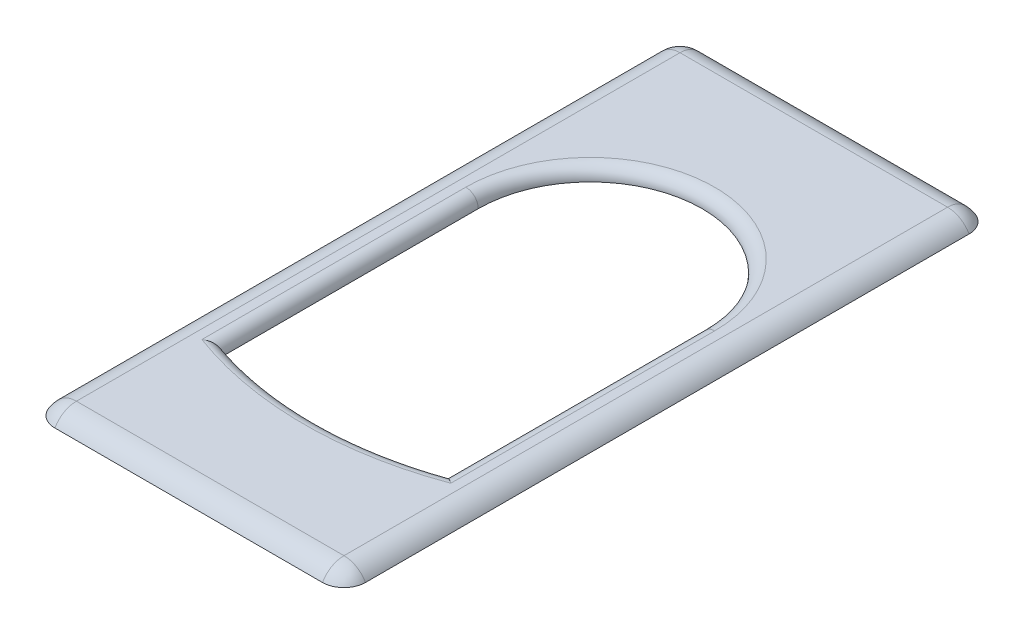
SolidWorks part; units mm, degrees
ref_plane "前视基准面" through (0, 0, 0) normal (0, 0, 1) x (1, 0, 0)
ref_plane "上视基准面" through (0, 0, 0) normal (0, 1, 0) x (1, 0, 0)
ref_plane "右视基准面" through (0, 0, 0) normal (1, 0, 0) x (0, 0, -1)
sketch "草图1" plane through (0, 0, 0) normal (0, 1, 0) x (1, 0, 0)
  line L8 (-8.3594, 36.0992) -> (13.1406, 36.0992)
  line L9 (15.1406, 34.0992) -> (15.1406, -14.4008)
  line L10 (13.1406, -16.4008) -> (-8.3594, -16.4008)
  line L11 (-10.3594, -14.4008) -> (-10.3594, 34.0992)
  line L14 (-6.6094, 16.1368) -> (-6.6094, -4.3632)
  line L15 (11.3906, 16.1368) -> (11.3906, -4.3632)
  arc A0 (-8.3594, 36.0992) -> (-10.3594, 34.0992) centre (-8.3594, 34.0992) ccw
  arc A1 (13.1406, 36.0992) -> (15.1406, 34.0992) centre (13.1406, 34.0992) cw
  arc A2 (15.1406, -14.4008) -> (13.1406, -16.4008) centre (13.1406, -14.4008) cw
  arc A3 (-8.3594, -16.4008) -> (-10.3594, -14.4008) centre (-8.3594, -14.4008) cw
  arc A4 (2.3906, 25.1368) -> (-6.6094, 16.1368) centre (2.3906, 16.1368) ccw
  arc A5 (2.3906, 25.1368) -> (11.3906, 16.1368) centre (2.3906, 16.1368) cw
  arc A6 (11.3906, -4.3632) -> (-6.6094, -4.3632) centre (2.3906, 21.8868) cw
extrude "凸台-拉伸1" add sketch "草图1" along normal blind 2
fillet "圆角1" radius 2 8 edges at (-9.7736, 2, 15.8151) (2.3906, 2, 16.4008) (14.5548, 2, 15.8151) (15.1406, 2, -9.8492) (-9.7736, 2, -35.5134) (14.5548, 2, -35.5134) (2.3906, 2, -36.0992) (-10.3594, 2, -9.8492)
sketch "草图2" plane through (0, 0, 0) normal (0, -1, 0) x (-1, 0, 0)
  line L1 (-17.3945, -18.8695) -> (18.3881, -18.8695)
  line L2 (-17.3945, -18.8695) -> (-17.3945, 40.2408)
  line L3 (-17.3945, 40.2408) -> (18.3881, 40.2408)
  line L4 (18.3881, -18.8695) -> (18.3881, 40.2408)
extrude "切除-拉伸1" cut sketch "草图2" against normal blind 1
fillet "圆角2" radius 1 4 edges at (11.3906, 2, -5.8868) (2.3906, 2, -25.1368) (-6.6094, 2, -5.8868) (2.3906, 2, 5.8632)
